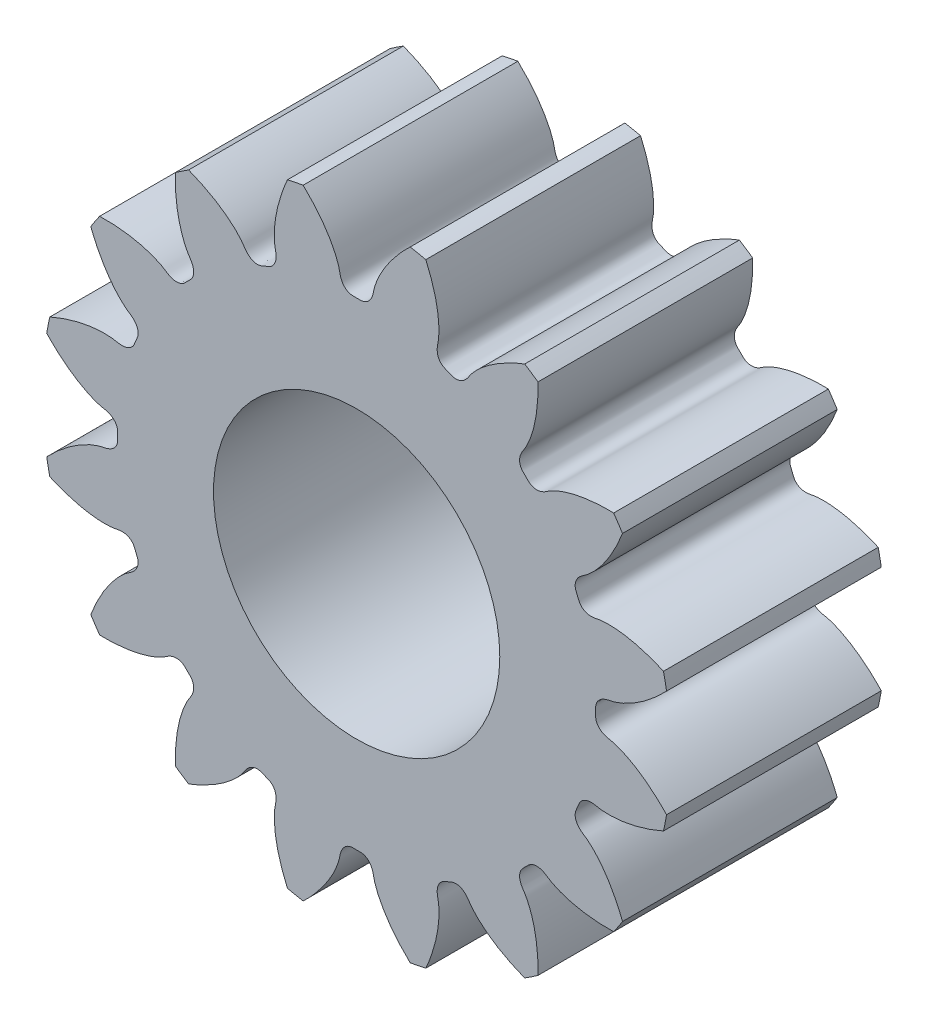
SolidWorks part; units mm, degrees
material "Д16 ГОСТ 4784-97"
ref_plane "FRONT" through (0, 0, 0) normal (0, 0, 1) x (1, 0, 0)
ref_plane "TOP" through (0, 0, 0) normal (0, 1, 0) x (1, 0, 0)
ref_plane "RIGHT" through (0, 0, 0) normal (1, 0, 0) x (0, 0, -1)
ref_axis "Ось1" through (0, 0, 50) along (0, 0, -1)
sketch "SketchRevolveSpurAssemblyNew1Pinion" plane through (0, 0, 0) normal (1, 0, 0) x (0, 0, -1)
  line L0 (0, 0) -> (1, 0) construction
  line L1 (-4, 0) -> (-4, 8.7891)
  line L2 (-4, 8.7891) -> (2, 8.7891)
  line L3 (2, 8.7891) -> (2, 0)
  line L4 (2, 0) -> (-4, 0)
  dimension "D1" = 4
  dimension "D2" = 6
revolve "SpurAssemblyNew1Pinion" add sketch "SketchRevolveSpurAssemblyNew1Pinion" angle 360 about L0
sketch "SketchToothSpurAssemblyNew1Pinion" plane through (0, 0, 0) normal (0, 0, 1) x (1, 0, 0)
  arc A0 (8.716, 1.5542) -> (8.716, -1.5542) centre (0, 0) cw
  spline S0 degree 3 poles (8.716, -1.5542) (8.6286, -1.4593) (8.496, -1.3253) (8.3141, -1.1618) (8.1849, -1.0543) (8.0598, -0.958) (7.9394, -0.8724) (7.8244, -0.797) (7.7153, -0.7313) (7.6127, -0.6747) (7.5171, -0.6266) (7.4291, -0.5864) (7.349, -0.5534) (7.2773, -0.5271) (7.2144, -0.5065) (7.1604, -0.4913) (7.098, -0.4758) (7.0463, -0.4679) (7.0043, -0.4578) (6.9857, -0.4529) (6.9673, -0.4474) (6.9491, -0.4414) (6.9309, -0.4347) (6.9128, -0.4273) (6.8947, -0.4192) (6.8765, -0.4101) (6.8582, -0.3999) (6.8397, -0.3884) (6.821, -0.3754) (6.8021, -0.3606) (6.7831, -0.3437) (6.7641, -0.3241) (6.7455, -0.3015) (6.7276, -0.2756) (6.7111, -0.246) (6.697, -0.2126) (6.6863, -0.1759) (6.68, -0.1381) (6.6779, -0.0791) (6.681, 0) (6.6779, 0.0791) (6.68, 0.1381) (6.6863, 0.1759) (6.697, 0.2126) (6.7111, 0.246) (6.7276, 0.2756) (6.7455, 0.3015) (6.7641, 0.3241) (6.7831, 0.3437) (6.8021, 0.3606) (6.821, 0.3754) (6.8397, 0.3884) (6.8582, 0.3999) (6.8765, 0.4101) (6.8947, 0.4192) (6.9128, 0.4273) (6.9309, 0.4347) (6.9491, 0.4414) (6.9673, 0.4474) (6.9857, 0.4529) (7.0043, 0.4578) (7.0463, 0.4679) (7.098, 0.4758) (7.1604, 0.4913) (7.2144, 0.5065) (7.2773, 0.5271) (7.349, 0.5534) (7.4291, 0.5864) (7.5171, 0.6266) (7.6127, 0.6747) (7.7153, 0.7313) (7.8244, 0.797) (7.9394, 0.8724) (8.0598, 0.958) (8.1849, 1.0543) (8.3141, 1.1618) (8.496, 1.3253) (8.6286, 1.4593) (8.716, 1.5542) knots 0 0 0 0 0.07194 0.10507 0.136308 0.165652 0.193102 0.21866 0.242325 0.264096 0.283974 0.301959 0.318051 0.33225 0.344555 0.354968 0.363487 0.380444 0.384031 0.387599 0.39116 0.394727 0.398315 0.401941 0.405627 0.409398 0.413281 0.41731 0.421523 0.425965 0.430682 0.435726 0.441147 0.446987 0.453273 0.460003 0.467133 0.474573 0.481319 0.5 0.518681 0.525427 0.532867 0.539997 0.546727 0.553013 0.558853 0.564274 0.569318 0.574035 0.578477 0.58269 0.586719 0.590602 0.594373 0.598059 0.601685 0.605273 0.60884 0.612401 0.615969 0.619556 0.636513 0.645032 0.655445 0.66775 0.681949 0.698041 0.716026 0.735904 0.757675 0.78134 0.806898 0.834348 0.863692 0.89493 0.92806 1 1 1 1
extrude "ToothExtrudeCutSpurAssemblyNew1Pinion" cut sketch "SketchToothSpurAssemblyNew1Pinion" against normal blind 4 and the other way blind 4
pattern_circular "PatternSpurAssemblyNew1Pinion" count 16 every 22.5 about axis through (0, 0, 50) along (0, 0, -1) of "ToothExtrudeCutSpurAssemblyNew1Pinion"
sketch "AuxiliarySketchSpurAssemblyNew1Pinion" plane through (0, 0, 0) normal (0, 0, 1) x (1, 0, 0)
  circle A0 centre (0, 0) radius 7.5 construction
  circle A1 centre (0, 0) radius 7.0477 construction
  circle A2 centre (0, 0) radius 7.0831 construction
  circle A3 centre (0, 0) radius 8.7891 construction
  circle A4 centre (0, 0) radius 6.6797 construction
  dimension "PitchDiameter" = 15
  dimension "BaseDiameter" = 14.0954
  dimension "FormDiameter" = 14.1663
  dimension "MajorDiameter" = 17.5781
  dimension "MinorDiameter" = 13.3594
sketch "Эскиз1" plane through (0, 0, 4) normal (0, 0, 1) x (1, 0, 0)
  circle A0 centre (0, 0) radius 4
extrude "Вырез-Вытянуть1" cut sketch "Эскиз1" against normal through all
